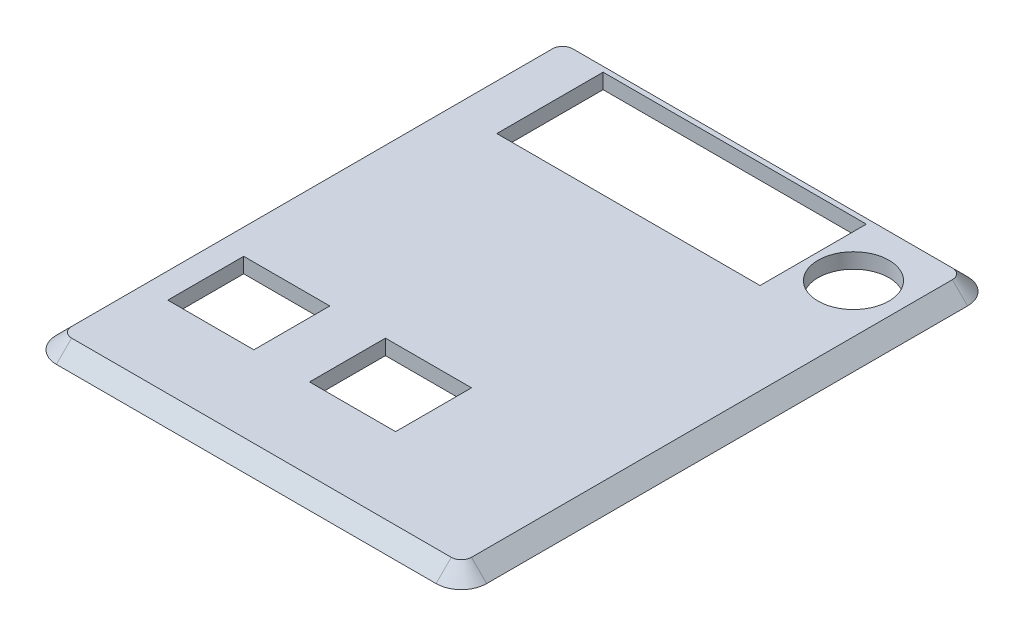
SolidWorks part; units mm, degrees
ref_plane "Front Plane" through (0, 0, 0) normal (0, 0, 1) x (1, 0, 0)
ref_plane "Top Plane" through (0, 0, 0) normal (0, 1, 0) x (1, 0, 0)
ref_plane "Right Plane" through (0, 0, 0) normal (1, 0, 0) x (0, 0, -1)
sketch "Sketch1" plane through (0, 0, 0) normal (0, 1, 0) x (1, 0, 0)
  line L1 (-42.5, -52.5) -> (42.5, -52.5)
  line L2 (-42.5, -52.5) -> (-42.5, 52.5)
  line L3 (-42.5, 52.5) -> (42.5, 52.5)
  line L4 (42.5, -52.5) -> (42.5, 52.5)
  line L5 (-42.5, -52.5) -> (42.5, 52.5) construction
  line L6 (-42.5, 52.5) -> (42.5, -52.5) construction
  point P0 (0, 0)
  dimension "D1" = 85
  dimension "D2" = 105
extrude "Boss-Extrude1" add sketch "Sketch1" along normal blind 3
sketch "Sketch2" plane through (0, 3, 0) normal (0, 1, 0) x (1, 0, 0)
  line L0 (-42.5, -52.5) -> (42.5, -52.5) construction
  line L1 (-34.5, -33.5) -> (-17.5, -33.5)
  line L2 (-34.5, -33.5) -> (-34.5, -18.5)
  line L3 (-34.5, -18.5) -> (-17.5, -18.5)
  line L4 (-17.5, -33.5) -> (-17.5, -18.5)
  line L5 (-34.5, -33.5) -> (-17.5, -18.5) construction
  line L6 (-34.5, -18.5) -> (-17.5, -33.5) construction
  line L7 (-6.5, -33.5) -> (10.5, -33.5)
  line L8 (-6.5, -33.5) -> (-6.5, -18.5)
  line L9 (-6.5, -18.5) -> (10.5, -18.5)
  line L10 (10.5, -33.5) -> (10.5, -18.5)
  line L11 (-6.5, -33.5) -> (10.5, -18.5) construction
  line L12 (-6.5, -18.5) -> (10.5, -33.5) construction
  line L13 (-42.5, 52.5) -> (-42.5, -52.5) construction
  point P0 (-26, -26)
  point P5 (2, -26)
  dimension "D1" = 19
  dimension "D2" = 19
  dimension "D3" = 34
  dimension "D4" = 34
  dimension "D5" = 8
  dimension "D6" = 25
  dimension "D7" = 36
  dimension "D8" = 53
extrude "Cut-Extrude1" cut sketch "Sketch2" against normal blind 10
fillet "Fillet1" radius 5 4 edges at (-42.5, 1.5, -52.5) (42.5, 1.5, -52.5) (42.5, 1.5, 52.5) (-42.5, 1.5, 52.5)
sketch "Sketch3" plane through (0, 3, 0) normal (0, 1, 0) x (1, 0, 0)
  line L0 (37.5, 52.5) -> (-37.5, 52.5) construction
  line L1 (-30.5, 48.5) -> (21.5, 48.5)
  line L2 (-30.5, 48.5) -> (-30.5, 27.5)
  line L3 (-30.5, 27.5) -> (21.5, 27.5)
  line L4 (21.5, 48.5) -> (21.5, 27.5)
  line L5 (-42.5, 47.5) -> (-42.5, -47.5) construction
  dimension "D1" = 4
  dimension "D2" = 25
  dimension "D3" = 12
  dimension "D4" = 64
extrude "Cut-Extrude2" cut sketch "Sketch3" against normal blind 10
fillet "Chamfer1" radius 3 8 edges at (41.0355, 3, -51.0355) (42.5, 3, 0) (41.0355, 3, 51.0355) (0, 3, 52.5) (-41.0355, 3, 51.0355) (-42.5, 3, 0) (-41.0355, 3, -51.0355) (0, 3, -52.5) profile chamfer
sketch "Sketch4" plane through (0, 3, 0) normal (0, 1, 0) x (1, 0, 0)
  circle A0 centre (29.8979, 37.5654) radius 7
  dimension "D1" = 14
extrude "Cut-Extrude3" cut sketch "Sketch4" against normal blind 10
